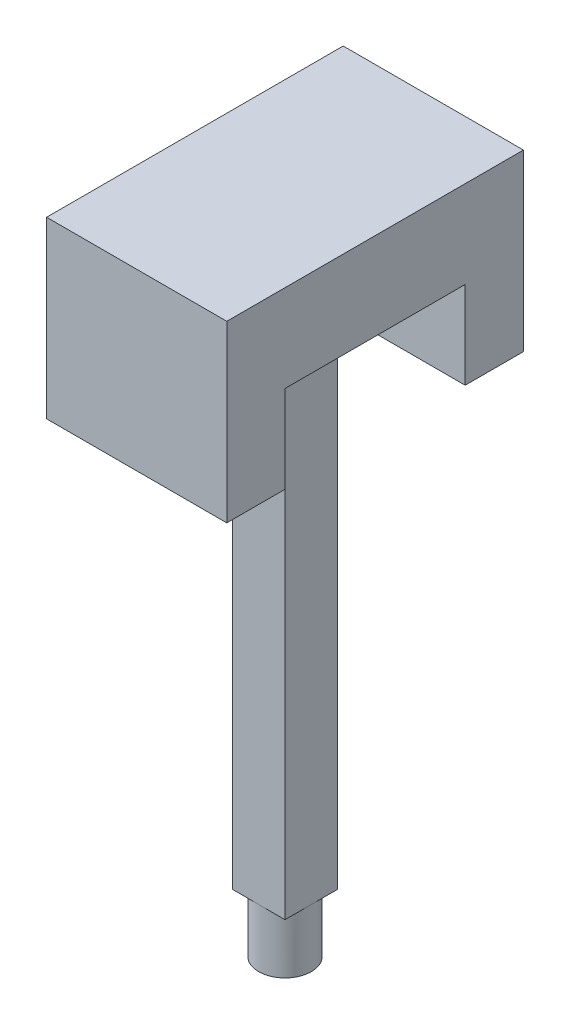
SolidWorks part; units mm, degrees
ref_plane "Front Plane" through (0, 0, 0) normal (0, 0, 1) x (1, 0, 0)
ref_plane "Top Plane" through (0, 0, 0) normal (0, 1, 0) x (1, 0, 0)
ref_plane "Right Plane" through (0, 0, 0) normal (1, 0, 0) x (0, 0, -1)
sketch "Sketch1" plane through (0, 0, 0) normal (0, 1, 0) x (1, 0, 0)
  line L5 (-0.7533, 0.7533) -> (0.7533, 0.7533)
  line L6 (-0.7533, 0.7533) -> (-0.7533, -0.7533)
  line L7 (-0.7533, -0.7533) -> (0.7533, -0.7533)
  line L8 (0.7533, 0.7533) -> (0.7533, -0.7533)
  line L9 (-0.7533, 0.7533) -> (0.7533, -0.7533) construction
  line L10 (-0.7533, -0.7533) -> (0.7533, 0.7533) construction
  point P4 (0, 0)
  point P5 (0, 0)
  dimension "D1" = 1.5067
extrude "Boss-Extrude1" add sketch "Sketch1" along normal blind 15 contours L5 L8 L7 L6
sketch "Sketch2" plane through (0, 0, 0) normal (0, -1, 0) x (1, 0, 0)
  circle A0 centre (0, 0) radius 0.7533
  dimension "D1" = 1.5067
extrude "Boss-Extrude2" add sketch "Sketch2" along normal blind 1.6667
sketch "Sketch3" plane through (0, 15, 0) normal (0, 1, 0) x (1, 0, 0)
  line L1 (-2.58, 2.58) -> (2.58, 2.58)
  line L2 (-2.58, 2.58) -> (-2.58, -2.58)
  line L3 (-2.58, -2.58) -> (2.58, -2.58)
  line L4 (2.58, 2.58) -> (2.58, -2.58)
  line L5 (-2.58, 2.58) -> (2.58, -2.58) construction
  line L6 (-2.58, -2.58) -> (2.58, 2.58) construction
  line L7 (-2.58, 2.58) -> (2.58, 2.58)
  line L8 (-2.58, 2.58) -> (-2.58, 4.2467)
  line L9 (-2.58, 4.2467) -> (2.58, 4.2467)
  line L10 (2.58, 2.58) -> (2.58, 4.2467)
  line L11 (-2.58, 2.58) -> (2.58, 4.2467) construction
  line L12 (-2.58, 4.2467) -> (2.58, 2.58) construction
  line L13 (-2.58, -2.58) -> (2.58, -2.58)
  line L14 (-2.58, -2.58) -> (-2.58, -4.2467)
  line L15 (-2.58, -4.2467) -> (2.58, -4.2467)
  line L16 (2.58, -2.58) -> (2.58, -4.2467)
  line L17 (-2.58, -2.58) -> (2.58, -4.2467) construction
  line L18 (-2.58, -4.2467) -> (2.58, -2.58) construction
  point P4 (0, 0)
  point P10 (0, 3.4133)
  point P13 (0, -3.4133)
  line M5 (-0.7533, 0.7533) -> (-0.7533, -0.7533)
  line M6 (-0.7533, -0.7533) -> (0.7533, -0.7533)
  line M7 (0.7533, -0.7533) -> (0.7533, 0.7533)
  line M8 (0.7533, 0.7533) -> (-0.7533, 0.7533)
  dimension "D1" = 5.16
  dimension "D2" = 1.6667
extrude "Boss-Extrude3" add sketch "Sketch3" along normal blind 2.5 contours L1 L10 L9 L8 | L4 L1 L2 L3 M5 M8 M7 M6 | L16 L3 L14 L15 | M8 M5 M6 M7 region at (0, 15, -3.4133) region at (0, 15, -2.507) region at (0, 15, 3.4133) region at (0, 15, 0)
extrude "Boss-Extrude4" add sketch "Sketch3<3>" against normal blind 2.5 contours L1 L10 L9 L8 | L16 L3 L14 L15 region at (0, 15, -3.4133) region at (0, 15, 3.4133)
sketch "Sketch3<3>" plane through (0, 15, 0) normal (0, 1, 0) x (1, 0, 0) same geometry as "Sketch3"
equation "\"Universal Bar Height\"= 5mm"
equation "\"D1@Sketch1\"=\"Universal Bar Height\"/3 - \"Pin Tolerance\""
equation "\"D1@Sketch2\"=\"Universal Bar Height\"/3 - \"Pin Tolerance\""
equation "\"D1@Boss-Extrude2\"=\"Universal Bar Height\"/3"
equation "\"D1@Sketch3\"=\"Universal Bar Height\" + \"Pin Tolerance\""
equation "\"D2@Sketch3\"=\"Universal Bar Height\"/3"
equation "\"D1@Boss-Extrude3\"=\"Universal Bar Height\"/2"
equation "\"Pin Tolerance\"= 0.16mm"
